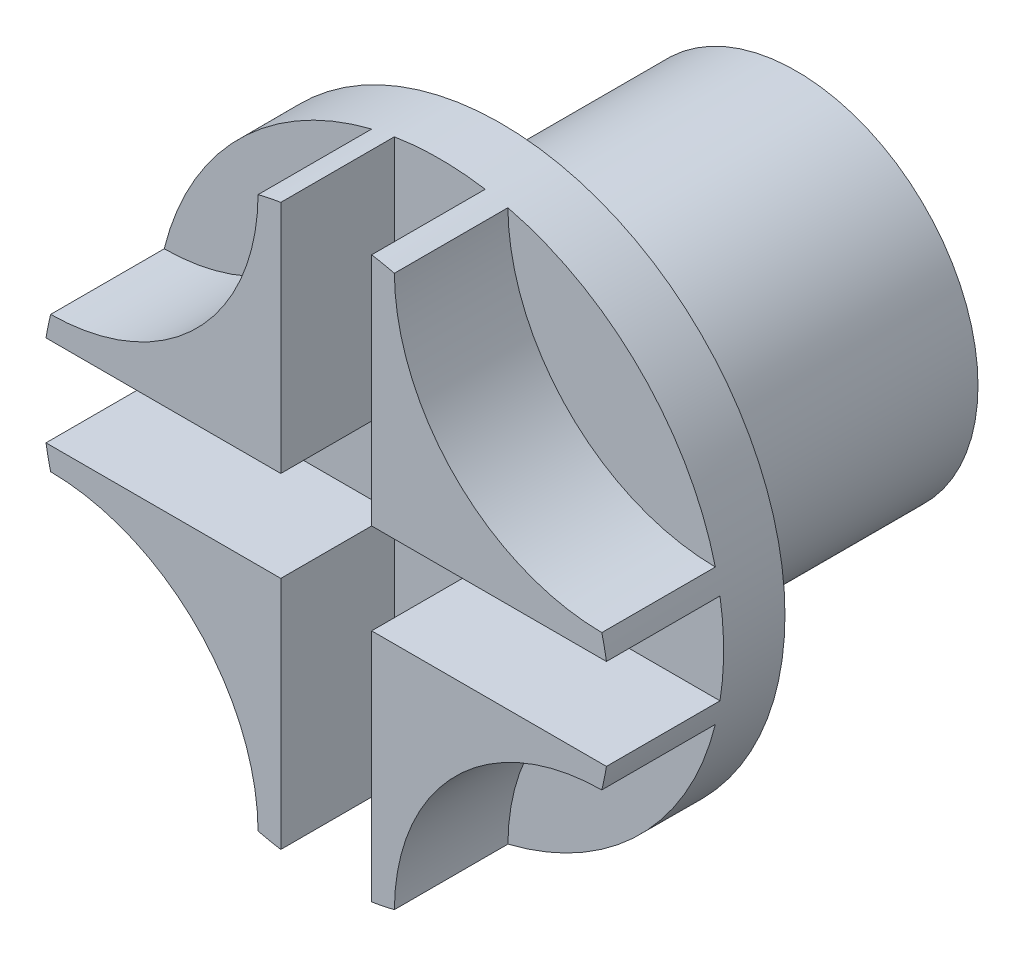
SolidWorks part; units mm, degrees
ref_plane "Alzado" through (0, 0, 0) normal (0, 0, 1) x (1, 0, 0)
ref_plane "Planta" through (0, 0, 0) normal (0, 1, 0) x (1, 0, 0)
ref_plane "Vista lateral" through (0, 0, 0) normal (1, 0, 0) x (0, 0, -1)
sketch "Croquis1" plane through (0, 0, 0) normal (0, 0, 1) x (1, 0, 0)
  line L0 (-2, 12.339) -> (-2, -12.339)
  line L1 (2, 12.339) -> (2, -12.339)
  line L2 (-2, 0) -> (2, 0) construction
  line L3 (0, -55) -> (0, 55) construction
  line L4 (55, 0) -> (-55, 0) construction
  line L5 (12.339, 2) -> (-12.339, 2)
  line L6 (-12.339, -2) -> (12.339, -2)
  line L7 (0, 2) -> (0, -2) construction
  line L8 (5.6944, 5.6944) -> (8.8388, 8.8388) construction
  circle A0 centre (0, 0) radius 12.5
  arc A1 (3, 12.1347) -> (12.1347, 3) centre (12.1998, 12.1998) ccw
  arc A2 (12.1347, -3) -> (3, -12.1347) centre (12.1998, -12.1998) ccw
  arc A3 (-3, -12.1347) -> (-12.1347, -3) centre (-12.1998, -12.1998) ccw
  arc A4 (-12.1347, 3) -> (-3, 12.1347) centre (-12.1998, 12.1998) ccw
  point P9 (0, 0)
  point P20 (0, 0)
  point P36 (0, 0)
  dimension "D4" = 25
  dimension "D6" = 9.2
  dimension "D1" = 4
  dimension "D2" = 4
  dimension "D3" = 1
  dimension "D5" = 1
  dimension "D7" = 4
extrude "Saliente-Extruir1" add sketch "Croquis1" along normal blind 2.7 contours A0
extrude "Saliente-Extruir2" add sketch "Croquis1<3>" along normal blind 5 from surface contours A4 A0 L5 L0 | A1 A0 L1 L5 | A2 A0 L6 L1 | A3 A0 L0 L6 region at (-4.9895, 4.9895, 0) region at (4.9895, 4.9895, 0) region at (-4.9895, -4.9895, 0) region at (4.9895, -4.9895, 0) starting at face at (12.5, 0, 2.7)
sketch "Croquis1<3>" plane through (0, 0, 0) normal (0, 0, 1) x (1, 0, 0) same geometry as "Croquis1"
sketch "Croquis2" plane through (0, 0, 0) normal (0, 0, -1) x (-1, 0, 0)
  circle A0 centre (0, 0) radius 8
  dimension "D1" = 16
extrude "Saliente-Extruir3" add sketch "Croquis2" along normal blind 13
equation "\"D2@Croquis1\"=\"D1@Croquis1\""
equation "\"D5@Croquis1\"=\"D3@Croquis1\""
